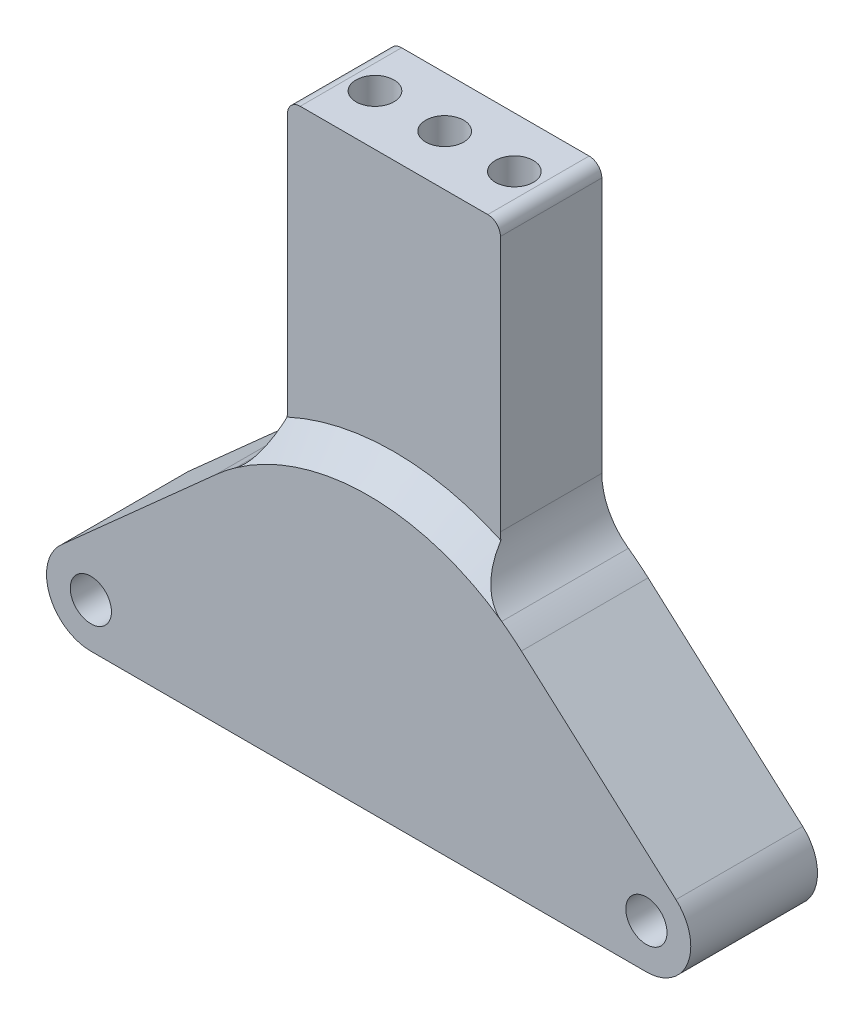
SolidWorks part; units mm, degrees
ref_plane "Front Plane" through (0, 0, 0) normal (0, 0, 1) x (1, 0, 0)
ref_plane "Top Plane" through (0, 0, 0) normal (0, 1, 0) x (1, 0, 0)
ref_plane "Right Plane" through (0, 0, 0) normal (1, 0, 0) x (0, 0, -1)
sketch "Sketch1" plane through (0, 0, 0) normal (0, 0, 1) x (1, 0, 0)
  line L0 (-21.92, 0) -> (21.92, 0) construction
  line L1 (0, 0) -> (0, 9.0384) construction
  line L2 (-21.92, 0) -> (21.92, 0) construction
  line L3 (-8.4, 40) -> (8.4, 40)
  line L4 (-8.4, 40) -> (-8.4, 0)
  line L5 (-8.4, 0) -> (8.4, 0)
  line L6 (8.4, 40) -> (8.4, 0)
  line L7 (-21.92, 3.5) -> (21.92, 3.5)
  line L8 (-21.92, -3.5) -> (21.92, -3.5)
  line L9 (-24.2512, 2.6106) -> (-12.0557, 13.5008)
  line L10 (24.2512, 2.6106) -> (12.0557, 13.5008)
  circle A0 centre (0, 0) radius 18.1
  circle A1 centre (21.92, 0) radius 1.625
  circle A2 centre (-21.92, 0) radius 1.625
  arc A3 (-21.92, 3.5) -> (-21.92, -3.5) centre (-21.92, 0) ccw
  arc A4 (21.92, -3.5) -> (21.92, 3.5) centre (21.92, 0) ccw
  point P13 (0, 0)
  dimension "D1" = 36.2
  dimension "D3" = 3.25
  dimension "D7" = 3.5
  dimension "D2" = 21.92
  dimension "D4" = 8.4
  dimension "D5" = 8.4
  dimension "D6" = 40
extrude "Boss-Extrude1" add sketch "Sketch1" along normal blind 10 contours A0 L6 L7 | L6 A0 L4 L7 | L4 A0 L7 | A3 L7 A0 L9 | A4 L7 A0 L8 A1 | A4 L10 A0 L7 | L7 A0 L8 L6 L5 L4 | L7 L4 L5 L6 | L7 A3 L8 A0 A2 region at (0, 10.4771, 0) region at (-12.0352, 8.2863, 0) region at (12.0352, 8.2863, 0) region at (0, 1.75, 0) region at (0, -0.5331, 0) region at (-18.6167, 6.1404, 0) region at (18.6167, 6.1404, 0) region at (-18.2038, 0, 0) region at (19.8392, 3.3962, 0)
extrude "Boss-Extrude2" add sketch "Sketch1<4>" along normal blind 8 contours A0 L6 L3 L4 region at (0, 28.7055, 0)
sketch "Sketch1<4>" plane through (0, 0, 0) normal (0, 0, 1) x (1, 0, 0) same geometry as "Sketch1"
sketch "Sketch2" plane through (0, 40, 0) normal (0, 1, 0) x (1, 0, 0)
  line L0 (-5.5, -4) -> (0, -4) construction
  line L1 (0, -4) -> (5.5, -4) construction
  line L2 (0, 0) -> (0, -8) construction
  line L3 (-8.4, -8) -> (8.4, -8) construction
  circle A0 centre (-5.5, -4) radius 1.5
  circle A1 centre (5.5, -4) radius 1.5
  circle A2 centre (0, -4) radius 1.5
  dimension "D1" = 3
  dimension "D2" = 5.5
  dimension "D3" = 4
extrude "Cut-Extrude1" cut sketch "Sketch2" against normal blind 30
fillet "Fillet1" radius 5 2 edges at (8.4, 16.0328, 4) (-8.4, 16.0328, 4)
chamfer "Chamfer1" distance 2 angle 45 1 edges at (0, 18.1, 8)
fillet "Fillet2" radius 1 2 edges at (8.4, 40, 4) (-8.4, 40, 4)
ref_plane "Plane1" through (0, 0, 0) normal (-1, 0, 0) x (0, 0, 1)
